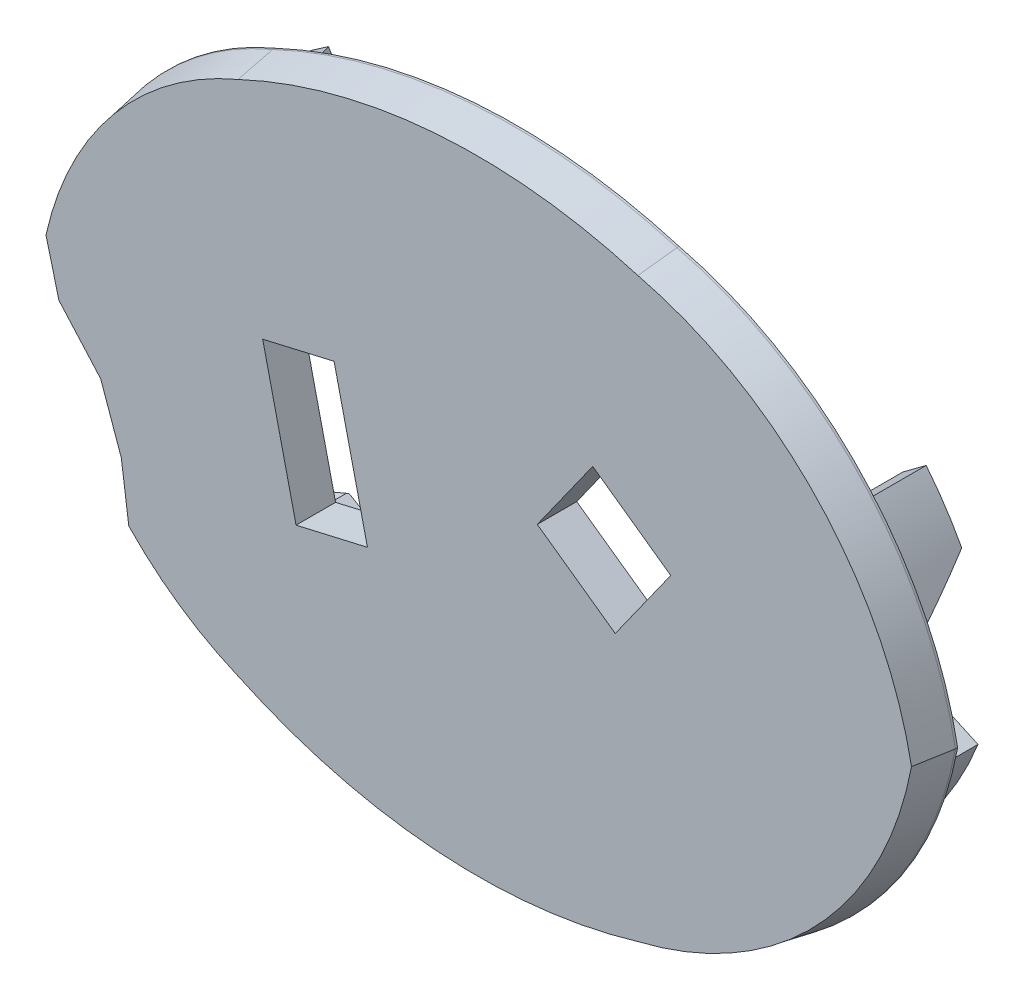
SolidWorks part; units mm, degrees
material "ABS"
ref_plane "Front Plane" through (0, 0, 0) normal (0, 0, 1) x (1, 0, 0)
ref_plane "Top Plane" through (0, 0, 0) normal (0, 1, 0) x (1, 0, 0)
ref_plane "Right Plane" through (0, 0, 0) normal (1, 0, 0) x (0, 0, -1)
sketch "Sketch1" plane through (0, 0, 0) normal (0, 0, 1) x (1, 0, 0)
  line L0 (-58.68, -17.7) -> (-56.84, -24.83)
  line L1 (-56.84, -24.83) -> (-51.2, -31.18)
  line L2 (-51.2, -31.18) -> (-48.53, -38.72)
  line L3 (-48.53, -38.72) -> (-47.49, -46.36)
  arc A0 (59.3165, -21.38) -> (21.92, 18.2) centre (10.0833, -30.4405) ccw
  arc A1 (21.92, 18.2) -> (-32.35, 14.11) centre (0.1355, -54.8406) ccw
  arc A2 (-32.35, 14.11) -> (-58.68, -17.7) centre (-14.9828, -27.0674) ccw
  arc A3 (-32.35, -56.87) -> (-47.49, -46.36) centre (-14.9831, -15.6925) cw
  arc A4 (21.9019, -60.95) -> (-32.35, -56.87) centre (0.1155, 12.09) cw
  arc A5 (59.3165, -21.38) -> (21.9019, -60.95) centre (10.0861, -12.3044) cw
  dimension "D7" = 44.69
  dimension "D8" = 76.22
  dimension "D9" = 50.06
  dimension "D10" = 50.06
  dimension "D11" = 76.22
  dimension "D12" = 44.69
  dimension "D1" = 12.09
  dimension "D2" = 32.35
  dimension "D3" = 21.92
  dimension "D4" = 21.38
  dimension "D5" = 60.95
  dimension "D6" = 56.87
  dimension "D13" = 7.64
  dimension "D14" = 7.54
  dimension "D15" = 6.35
  dimension "D16" = 7.13
  dimension "D17" = 46.36
  dimension "D18" = 18.2
  dimension "D19" = 15.91
  dimension "D20" = 32.35
  dimension "D21" = 14.11
  dimension "D22" = 58.68
  dimension "D23" = 56.84
  dimension "D24" = 51.2
  dimension "D25" = 48.53
  dimension "D26" = 47.49
extrude "Boss-Extrude1" add sketch "Sketch1" along normal blind 5.3
chamfer "Chamfer1" distance 5 angle 10 10 edges at (46.4705, 3.9394, 5.3) (46.4606, -46.6977, 5.3) (-5.6005, -63.9154, 5.3) (-40.4677, -52.404, 5.3) (-48.01, -42.54, 5.3) (-49.865, -34.95, 5.3) (-54.02, -28.005, 5.3) (-57.76, -21.265, 5.3) (-5.5925, 21.1639, 5.3) (-49.4093, 1.4284, 5.3) first distance on face at (43.5444, 1.1747, 2.65) first distance on face at (43.5349, -43.9313, 2.65) first distance on face at (-5.4123, -61.4127, 2.65) first distance on face at (-40.1938, -52.0095, 2.65) first distance on face at (-48.01, -42.54, 2.65) first distance on face at (-49.865, -34.95, 2.65) first distance on face at (-54.02, -28.005, 2.65) first distance on face at (-57.76, -21.265, 2.65) first distance on face at (-5.4037, 18.6594, 2.65) first distance on face at (-47.4622, -0.1833, 2.65)
sketch "Sketch2" plane through (0, 0, 0) normal (0, 0, -1) x (-1, 0, 0)
  line L0 (31.28, 9.85) -> (27.74, 3.91)
  line L1 (42.8125, -9.07) -> (46.88, -3.39)
  line L2 (26.6873, -46.74) -> (31.03, -53.17)
  line L3 (39.0078, -42.3893) -> (40.4, -36.69)
  line L4 (40.4, -36.69) -> (43.503, -30.0375)
  line L5 (43.503, -30.0375) -> (48.691, -24.74)
  line L6 (48.691, -24.74) -> (53.3699, -18.25)
  line L7 (-19.97, 14.41) -> (-19.2, 12.43)
  line L8 (-41.46, -3.51) -> (-44.5926, -1.18)
  line L9 (-44.86, -27.08) -> (-51.55, -30.14)
  line L10 (-32.8814, -43.2025) -> (-38.7619, -48.0193)
  line L11 (-44.8655, -9.31) -> (-41.46, -3.51)
  line L12 (39.0078, -42.3893) -> (33.015, -43.11)
  line L13 (33.015, -43.11) -> (26.6873, -46.74)
  line L14 (43.19, -44.34) -> (39.0078, -42.3893)
  line L15 (-49.8215, -14.39) -> (-51.9132, -14.0361)
  line L16 (-41.46, -3.51) -> (-44.8655, -9.31)
  line L17 (9.73, 13.95) -> (10.6, 16.46)
  line L18 (-4.72, 14.7764) -> (-4.88, 17.1356)
  line L19 (-32.8814, -43.2025) -> (-31.6661, -49.99)
  line L20 (-44.8655, -9.31) -> (-49.8215, -14.39)
  line L21 (44.1299, -37.38) -> (43.1777, -44.34)
  line L22 (46.5607, -30.52) -> (44.1299, -37.38)
  line L23 (51.6952, -24.74) -> (46.5607, -30.52)
  line L24 (53.3699, -18.25) -> (51.6952, -24.74)
  line L25 (-31.6661, -49.99) -> (-24.69, -53.51)
  line L26 (-24.69, -53.51) -> (-25.532, -55.8863)
  arc A0 (27.74, 3.91) -> (42.8125, -9.07) centre (19.0675, -21.4018) cw
  arc A1 (-4.72, 14.7764) -> (9.73, 13.95) centre (-0.0347, -30.0465) cw
  arc A2 (-44.86, -27.08) -> (-32.8814, -43.2025) centre (-10.3522, -13.9528) ccw
  arc A3 (-19.2, 12.43) -> (-43.0263, -2.345) centre (-9.4071, -29.9608) ccw
  arc A4 (-51.55, -30.14) -> (-25.532, -55.8863) centre (-9.1996, -13.3621) ccw
  arc A5 (31.03, -53.17) -> (43.1777, -44.34) centre (13.601, -16.4214) ccw
  arc A6 (46.88, -3.39) -> (31.28, 9.85) centre (13.6079, -26.7823) ccw
  arc A7 (10.6, 16.46) -> (-4.88, 17.1356) centre (-0.1455, -52.0641) ccw
  arc A8 (-19.97, 14.41) -> (-51.9132, -14.0361) centre (-9.1934, -29.8497) ccw
  dimension "D1" = 45.0671
  dimension "D2" = 69.3615
  dimension "D3" = 26.7563
  dimension "D4" = 40.6722
  dimension "D5" = 36.9204
  dimension "D6" = 45.5528
  dimension "D7" = 45.5528
  dimension "D8" = 43.5072
  dimension "D9" = 40.6722
  dimension "D10" = 27.74
  dimension "D11" = 31.28
  dimension "D12" = 42.8125
  dimension "D13" = 46.88
  dimension "D14" = 13.95
  dimension "D15" = 16.46
  dimension "D16" = 14.7764
  dimension "D17" = 17.1356
  dimension "D18" = 9.73
  dimension "D19" = 4.72
  dimension "D20" = 10.6
  dimension "D21" = 4.88
  dimension "D22" = 3.91
  dimension "D23" = 9.85
  dimension "D24" = 9.07
  dimension "D25" = 3.39
  dimension "D26" = 44.86
  dimension "D27" = 51.55
  dimension "D28" = 38.7619
  dimension "D29" = 32.8814
  dimension "D30" = 31.6661
  dimension "D31" = 24.69
  dimension "D32" = 25.532
  dimension "D33" = 30.14
  dimension "D34" = 27.08
  dimension "D35" = 48.0193
  dimension "D36" = 43.2025
  dimension "D37" = 49.99
  dimension "D38" = 53.51
  dimension "D39" = 31.03
  dimension "D40" = 26.6873
  dimension "D41" = 43.19
  dimension "D42" = 33.015
  dimension "D43" = 39.0078
  dimension "D44" = 40.4
  dimension "D45" = 44.1299
  dimension "D46" = 43.503
  dimension "D47" = 46.5607
  dimension "D48" = 48.691
  dimension "D49" = 51.6952
  dimension "D50" = 53.3699
  dimension "D51" = 53.17
  dimension "D52" = 46.74
  dimension "D53" = 43.11
  dimension "D54" = 44.34
  dimension "D55" = 42.3893
  dimension "D56" = 36.69
  dimension "D57" = 24.74
  dimension "D58" = 18.25
  dimension "D59" = 24.74
  dimension "D60" = 30.52
  dimension "D61" = 37.38
  dimension "D62" = 13.601
  dimension "D63" = 6.96
  dimension "D64" = 19.2
  dimension "D65" = 19.97
  dimension "D66" = 44.5926
  dimension "D67" = 41.46
  dimension "D68" = 51.9132
  dimension "D69" = 49.8215
  dimension "D70" = 44.8655
  dimension "D71" = 14.41
  dimension "D72" = 12.43
  dimension "D73" = 3.51
  dimension "D74" = 1.18
  dimension "D75" = 14.39
  dimension "D76" = 9.31
extrude "Boss-Extrude2" add sketch "Sketch2" along normal blind 10.5 contours L9 A4 L10 A2 | L2 A5 L21 L14 L12 L13 | L1 A6 L0 A0 | L8 A8 L15 L20 L11 region at (-37.7951, 1.2192, 0) region at (-34.4261, -46.9883, 0) region at (46.6222, -7.7499, 0) region at (42.7822, -37.6962, 0)
ref_plane "Plane1" through (0, 0, -2.5) normal (0, 0, -1) x (-1, 0, 0)
sketch "Sketch3" plane through (0, 0, -2.5) normal (0, 0, -1) x (-1, 0, 0)
  line L0 (-24.69, -53.51) -> (-25.532, -55.8863) construction
  line L1 (-31.6661, -49.99) -> (-24.69, -53.51) construction
  line L2 (-32.8814, -43.2025) -> (-31.6661, -49.99) construction
  line L3 (-32.8814, -43.2025) -> (-38.7619, -48.0193) construction
  line L4 (-44.86, -27.08) -> (-51.55, -30.14) construction
  line L5 (43.19, -44.34) -> (39.0078, -42.3893) construction
  line L6 (26.6873, -46.74) -> (31.03, -53.17) construction
  line L7 (33.015, -43.11) -> (26.6873, -46.74) construction
  line L8 (39.0078, -42.3893) -> (33.015, -43.11) construction
  line L9 (44.1299, -37.38) -> (43.1777, -44.34) construction
  line L10 (39.0078, -42.3893) -> (40.4, -36.69) construction
  line L11 (46.5607, -30.52) -> (44.1299, -37.38) construction
  line L12 (40.4, -36.69) -> (43.503, -30.0375) construction
  line L13 (43.503, -30.0375) -> (48.691, -24.74) construction
  line L14 (51.6952, -24.74) -> (46.5607, -30.52) construction
  line L15 (53.3699, -18.25) -> (51.6952, -24.74) construction
  line L16 (48.691, -24.74) -> (53.3699, -18.25) construction
  line L17 (42.8125, -9.07) -> (46.88, -3.39) construction
  line L18 (31.28, 9.85) -> (27.74, 3.91) construction
  line L19 (9.73, 13.95) -> (10.6, 16.46) construction
  line L20 (-4.72, 14.7764) -> (-4.88, 17.1356) construction
  line L21 (-19.97, 14.41) -> (-19.2, 12.43) construction
  line L22 (-41.46, -3.51) -> (-44.5926, -1.18) construction
  line L23 (-44.8655, -9.31) -> (-41.46, -3.51) construction
  line L24 (-44.8655, -9.31) -> (-49.8215, -14.39) construction
  line L25 (-49.8215, -14.39) -> (-51.9132, -14.0361) construction
  line L26 (-24.69, -53.51) -> (-25.532, -55.8863)
  line L27 (-31.6661, -49.99) -> (-24.69, -53.51)
  line L28 (-32.8814, -43.2025) -> (-31.6661, -49.99)
  line L29 (-32.8814, -43.2025) -> (-38.7619, -48.0193)
  line L30 (-44.86, -27.08) -> (-51.55, -30.14)
  line L31 (43.19, -44.34) -> (39.0078, -42.3893)
  line L32 (26.6873, -46.74) -> (31.03, -53.17)
  line L33 (33.015, -43.11) -> (26.6873, -46.74)
  line L34 (39.0078, -42.3893) -> (33.015, -43.11)
  line L35 (44.1299, -37.38) -> (43.1777, -44.34)
  line L36 (39.0078, -42.3893) -> (40.4, -36.69)
  line L37 (46.5607, -30.52) -> (44.1299, -37.38)
  line L38 (40.4, -36.69) -> (43.503, -30.0375)
  line L39 (43.503, -30.0375) -> (48.691, -24.74)
  line L40 (51.6952, -24.74) -> (46.5607, -30.52)
  line L41 (53.3699, -18.25) -> (51.6952, -24.74)
  line L42 (48.691, -24.74) -> (53.3699, -18.25)
  line L43 (42.8125, -9.07) -> (46.88, -3.39)
  line L44 (31.28, 9.85) -> (27.74, 3.91)
  line L45 (9.73, 13.95) -> (10.6, 16.46)
  line L46 (-4.72, 14.7764) -> (-4.88, 17.1356)
  line L47 (-19.97, 14.41) -> (-19.2, 12.43)
  line L48 (-41.46, -3.51) -> (-44.5926, -1.18)
  line L49 (-44.8655, -9.31) -> (-41.46, -3.51)
  line L50 (-44.8655, -9.31) -> (-49.8215, -14.39)
  line L51 (-49.8215, -14.39) -> (-51.9132, -14.0361)
  arc A0 (-44.86, -27.08) -> (-32.8814, -43.2025) centre (-10.3522, -13.9528) ccw construction
  arc A1 (-51.55, -30.14) -> (-25.532, -55.8863) centre (-9.1996, -13.3621) ccw construction
  arc A2 (31.03, -53.17) -> (43.1777, -44.34) centre (13.601, -16.4214) ccw construction
  arc A3 (46.88, -3.39) -> (31.28, 9.85) centre (13.6079, -26.7823) ccw construction
  arc A4 (42.8125, -9.07) -> (27.74, 3.91) centre (19.0675, -21.4018) ccw construction
  arc A5 (10.6, 16.46) -> (-4.88, 17.1356) centre (-0.1455, -52.0641) ccw construction
  arc A6 (9.73, 13.95) -> (-4.72, 14.7764) centre (-0.0347, -30.0465) ccw construction
  arc A7 (-19.2, 12.43) -> (-43.0263, -2.345) centre (-9.4071, -29.9608) ccw construction
  arc A8 (-19.97, 14.41) -> (-51.9132, -14.0361) centre (-9.1934, -29.8497) ccw construction
  arc A9 (-44.86, -27.08) -> (-32.8814, -43.2025) centre (-10.3522, -13.9528) ccw
  arc A10 (-51.55, -30.14) -> (-25.532, -55.8863) centre (-9.1996, -13.3621) ccw
  arc A11 (31.03, -53.17) -> (43.1777, -44.34) centre (13.601, -16.4214) ccw
  arc A12 (46.88, -3.39) -> (31.28, 9.85) centre (13.6079, -26.7823) ccw
  arc A13 (42.8125, -9.07) -> (27.74, 3.91) centre (19.0675, -21.4018) ccw
  arc A14 (10.6, 16.46) -> (-4.88, 17.1356) centre (-0.1455, -52.0641) ccw
  arc A15 (9.73, 13.95) -> (-4.72, 14.7764) centre (-0.0347, -30.0465) ccw
  arc A16 (-19.2, 12.43) -> (-43.0263, -2.345) centre (-9.4071, -29.9608) ccw
  arc A17 (-19.97, 14.41) -> (-51.9132, -14.0361) centre (-9.1934, -29.8497) ccw
extrude "Boss-Extrude3" add sketch "Sketch3" against normal up to surface (2.5 mm away) contours L47 A17 L48 A16 | L42 L39 L38 L36 L31 L35 L37 L40 L41 | L29 A10 L26 L27 L28 | A15 L45 A14 L46 region at (32.2117, -49.9541, -2.5) region at (-44.8206, -33.1707, -2.5) region at (-2.8403, 15.9212, -2.5) region at (32.3782, 7.2605, -2.5) up to face at (-37.7024, 0.9374, 0)
chamfer "Chamfer2" distance 6 angle 55 1 edges at (50.8674, -14.2131, -10.5) first distance on face at (46.6356, -8.4254, -10.5)
chamfer "Chamfer3" distance 6 angle 53 1 edges at (35.8217, -45.6109, -10.5) first distance on face at (42.5664, -37.5138, -10.5)
chamfer "Chamfer4" distance 5 angle 60 1 edges at (-29.51, 6.88, -10.5) first distance on face at (-37.7024, 0.9374, -10.5)
sketch "Sketch4" plane through (0, 0, -10.5) normal (0, 0, -1) x (-1, 0, 0)
  line L0 (39.0078, -42.3893) -> (43.1784, -44.3346)
  line L1 (43.1784, -44.3346) -> (39.4433, -40.6065)
  line L3 (39.4433, -40.6065) -> (39.0078, -42.3893)
  line L4 (39.0078, -42.3893) -> (40.4, -36.69) construction
  dimension "D1" = 19.94
extrude "Boss-Extrude4" add sketch "Sketch4" against normal blind 10.5
chamfer "Chamfer5" distance 6.5 angle 50 1 edges at (-41.3109, -42.4705, -10.5) first distance on face at (-36.5644, -45.0366, -10.5)
sketch "Sketch5" plane through (0, 0, 0) normal (0, 0, -1) x (-1, 0, 0)
  line L0 (-26.1, -15.32) -> (-15.63, -7.87)
  line L1 (-15.63, -7.87) -> (-8.18, -18.34)
  line L2 (-8.18, -18.34) -> (-18.65, -25.7899)
  line L3 (-18.65, -25.7899) -> (-26.1, -15.32)
  line L4 (19.1, -13.02) -> (28.6835, -15.2368)
  line L5 (28.6835, -15.2368) -> (24.2, -34.62)
  line L6 (24.2, -34.62) -> (14.6165, -32.4032)
  line L7 (14.6165, -32.4032) -> (19.1, -13.02)
  dimension "D1" = 12.85
  dimension "D2" = 12.85
  dimension "D3" = 9.8366
  dimension "D4" = 19.895
  dimension "D5" = 15.63
  dimension "D6" = 7.87
  dimension "D7" = 13.02
  dimension "D8" = 19.1
  dimension "D9" = 18.65
  dimension "D10" = 34.62
  dimension "D11" = 24.2
extrude "Cut-Extrude1" cut sketch "Sketch5" against normal blind 10.5
ref_plane "Plane2" through (57.5197, 0, 10.3176) normal (0.9843, 0, 0.1766) x (0.1766, 0, -0.9843)
